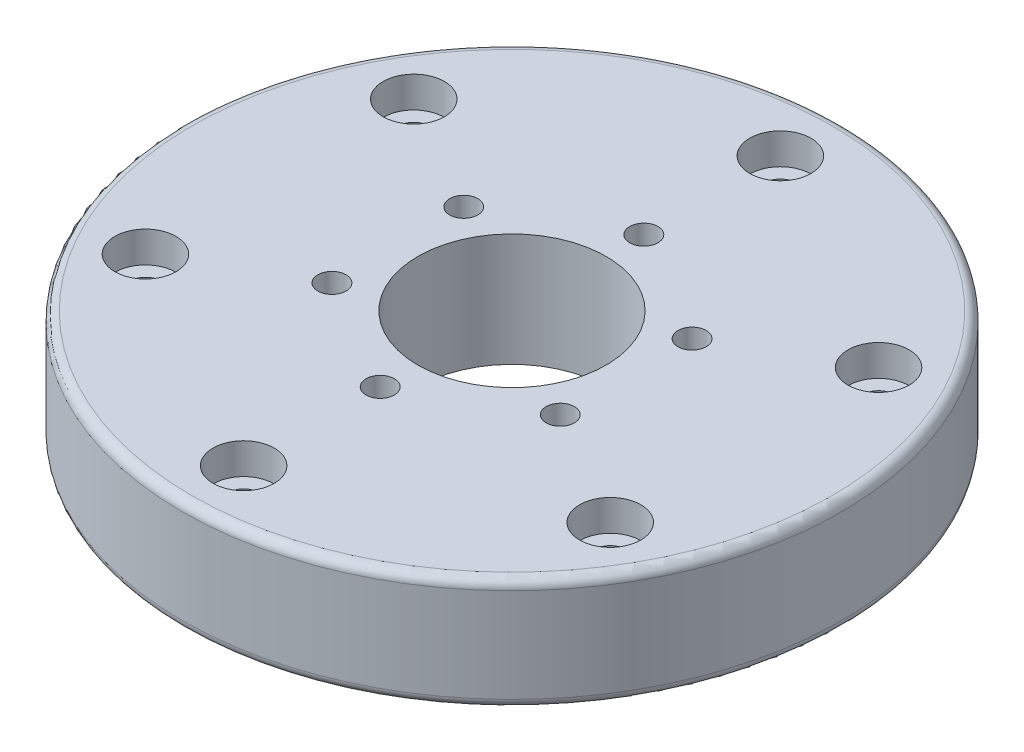
SolidWorks part; units mm, degrees
note: '?' marks a value the reader was unsure of.
ref_plane "前视基准面" through (0, 0, 0) normal (0, 0, 1) x (1, 0, 0)
ref_plane "上视基准面" through (0, 0, 0) normal (0, 1, 0) x (1, 0, 0)
ref_plane "右视基准面" through (0, 0, 0) normal (1, 0, 0) x (0, 0, -1)
sketch "草图1" plane through (0, 0, 0) normal (0, 1, 0) x (1, 0, 0)
  circle A0 centre (0, 0) radius 35
  dimension "D1" = 70
extrude "凸台-拉伸1" add sketch "草图1" along normal blind 12
sketch "草图2" plane through (0, 12, 0) normal (0, 1, 0) x (1, 0, 0)
  circle A0 centre (0, 0) radius 28.5
  dimension "D1" = 57
sketch "草图3" plane through (0, 12, 0) normal (0, 1, 0) x (1, 0, 0)
  circle A0 centre (0, 0) radius 28.5 construction
  point P0 (0, 28.5)
hole_wizard "孔1" positions "草图3" profile "草图4" legacy
sketch "草图4" plane through (0, 12, -28.5) normal (1, 0, 0) x (0, 0, 1)
  line L0 (0, 0) -> (0, 3.3)
  line L1 (0, 3.3) -> (3.25, 3.3)
  line L2 (3.25, 3.3) -> (3.25, 0)
  line L3 (3.25, 0) -> (0, 0)
  line L4 (0, 110) -> (0, -10) construction
  dimension "直径" = 6.5
  dimension "深度" = 3.3
ref_axis "基准轴1" through (0, 0, 0) along (0, 1, 0)?
pattern_circular "阵列(圆周)1" count 6 every 60 about axis through (0, 0, 0) along (0, 1, 0) of "孔1"
sketch "草图5" plane through (0, 8.7, 0) normal (0, 1, 0) x (1, 0, 0)
  point P0 (0, 28.5)
hole_wizard "孔2" positions "草图5" profile "草图6" legacy end condition up to next
sketch "草图6" plane through (0, 8.7, -28.5) normal (1, 0, 0) x (0, 0, 1)
  line L0 (0, 0) -> (0, 8.7)
  line L1 (0, 8.7) -> (1.65, 8.7)
  line L2 (1.65, 8.7) -> (1.65, 0)
  line L3 (1.65, 0) -> (0, 0)
  line L4 (0, 110) -> (0, -10) construction
  dimension "直径" = 3.3
  dimension "深度" = 8.7
pattern_circular "阵列(圆周)2" count 6 every 60 about axis through (0, 0, 0) along (0, 1, 0) of "孔2"
sketch "草图7" plane through (0, 12, 0) normal (0, 1, 0) x (1, 0, 0)
  circle A0 centre (0, 0) radius 14
  dimension "D1" = 28
sketch "草图8" plane through (0, 12, 0) normal (0, 1, 0) x (1, 0, 0)
  circle A0 centre (0, 0) radius 14 construction
  point P0 (0, 14)
hole_wizard "孔3" positions "草图8" profile "草图9" legacy end condition up to next
sketch "草图9" plane through (0, 12, -14) normal (1, 0, 0) x (0, 0, 1)
  line L0 (0, 0) -> (0, 12)
  line L1 (0, 12) -> (1.5, 12)
  line L2 (1.5, 12) -> (1.5, 0)
  line L3 (1.5, 0) -> (0, 0)
  line L4 (0, 110) -> (0, -10) construction
  dimension "直径" = 3
  dimension "深度" = 12
pattern_circular "阵列(圆周)3" count 6 every 60 about axis through (0, 0, 0) along (0, 1, 0) of "孔3"
sketch "草图10" plane through (0, 12, 0) normal (0, 1, 0) x (1, 0, 0)
  circle A0 centre (0, 0) radius 21
  dimension "D1" = 42
fillet "圆角1" radius 1 2 edges at (0, 0, 35) (0, 12, 35)
hole_wizard "孔4" positions "草图11" profile "草图12" legacy end condition up to next
sketch "草图11" plane through (0, 12, 0) normal (0, 1, 0) x (1, 0, 0)
  point P0 (0, 0)
sketch "草图12" plane through (0, 12, 0) normal (1, 0, 0) x (0, 0, 1)
  line L0 (0, 0) -> (0, 12)
  line L1 (0, 12) -> (10, 12)
  line L2 (10, 12) -> (10, 0)
  line L3 (10, 0) -> (0, 0)
  line L4 (0, 110) -> (0, -10) construction
  dimension "直径" = 20
  dimension "深度" = 12
